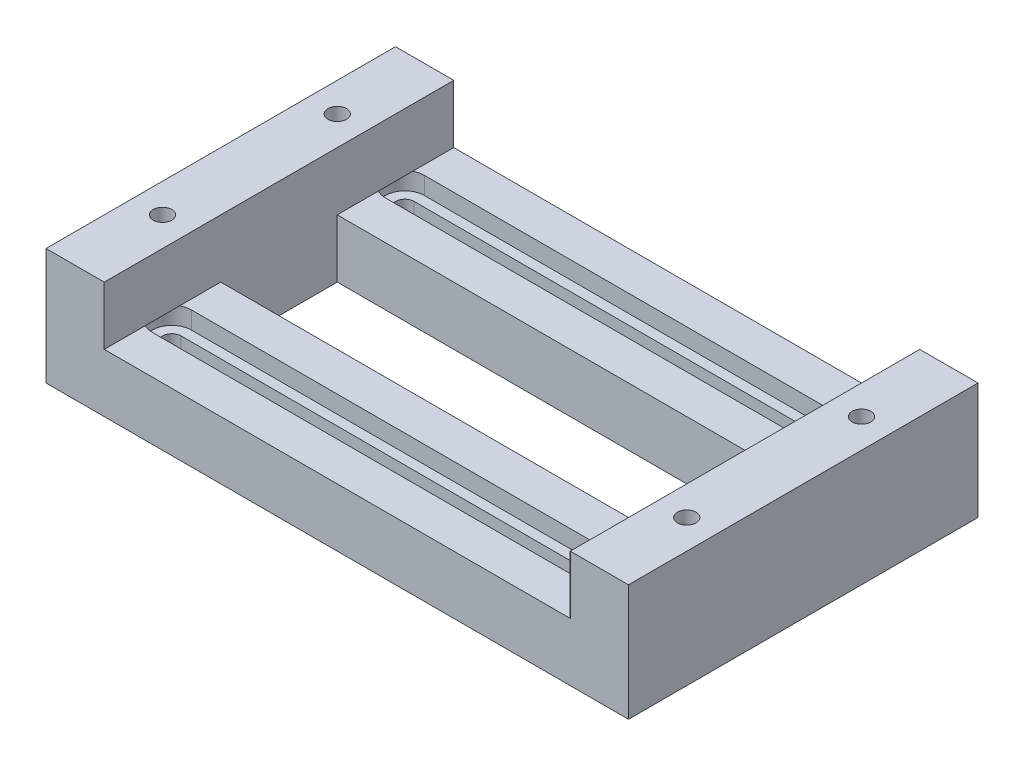
SolidWorks part; units mm, degrees
ref_plane "Front Plane" through (0, 0, 0) normal (0, 0, 1) x (1, 0, 0)
ref_plane "Top Plane" through (0, 0, 0) normal (0, 1, 0) x (1, 0, 0)
ref_plane "Right Plane" through (0, 0, 0) normal (1, 0, 0) x (0, 0, -1)
sketch "Sketch1" plane through (0, 0, 0) normal (0, 1, 0) x (1, 0, 0)
  line L0 (10, 40) -> (10, 20)
  line L1 (0, 0) -> (100, 0)
  line L2 (0, 0) -> (0, 60)
  line L3 (0, 60) -> (100, 60)
  line L4 (100, 0) -> (100, 60)
  line L5 (10, 20) -> (90, 20)
  line L6 (90, 20) -> (90, 40)
  line L7 (90, 40) -> (10, 40)
  line L8 (11.6, 10) -> (88.4, 10) construction
  line L9 (11.6, 11.6) -> (88.4, 11.6)
  line L10 (11.6, 8.4) -> (88.4, 8.4)
  line L11 (88.4, 50) -> (11.6, 50) construction
  line L12 (88.4, 48.4) -> (11.6, 48.4)
  line L13 (50, 0) -> (50, 20) construction
  line L14 (50, 40) -> (50, 60)
  line L15 (88.4, 51.6) -> (11.6, 51.6)
  circle A7 centre (5, 45) radius 1.6
  arc A22 (11.6, 11.6) -> (11.6, 8.4) centre (11.6, 10) ccw
  arc A23 (88.4, 8.4) -> (88.4, 11.6) centre (88.4, 10) ccw
  arc A24 (88.4, 48.4) -> (88.4, 51.6) centre (88.4, 50) ccw
  arc A25 (11.6, 51.6) -> (11.6, 48.4) centre (11.6, 50) ccw
  circle A29 centre (5, 15) radius 1.6
  circle A46 centre (95, 45) radius 1.6
  circle A47 centre (95, 15) radius 1.6
  point P14 (50, 50)
  point P17 (50, 10)
  point P22 (50, 50)
  point P33 (50, 10)
  point P34 (90, 10)
  point P35 (10, 10)
  point P36 (90, 50)
  point P37 (10, 50)
  dimension "D25" = 3.2
  dimension "D4" = 3.2
  dimension "D18" = 3.2
  dimension "D19" = 3.2
  dimension "D1" = 60
  dimension "D2" = 100
  dimension "D3" = 10
  dimension "D22" = 20
  dimension "D23" = 20
  dimension "D24" = 10
  dimension "D28" = 15
  dimension "D5" = 15
  dimension "D6" = 5
  dimension "D8" = 5
  dimension "D9" = 15
  dimension "D13" = 5
  dimension "D16" = 5
  dimension "D17" = 15
  dimension "D7" = 3.2
  dimension "D10" = 3.2
  dimension "D11" = 80
  dimension "D12" = 80
extrude "Boss-Extrude1" add sketch "Sketch1" along normal blind 10 contours L1 L4 L3 L2 A47 A46 A29 A7 L7 L6 L5 L0 region at (75, 0, -58.8338)
sketch "Sketch3" plane through (0, 10, 0) normal (0, 1, 0) x (1, 0, 0)
  line L4 (88.4, 53.35) -> (11.6, 53.35)
  line L5 (11.6, 46.65) -> (88.4, 46.65)
  line L6 (88.4, 13.35) -> (11.6, 13.35)
  line L7 (11.6, 6.65) -> (88.4, 6.65)
  line L8 (88.4, 13.35) -> (11.6, 13.35)
  line L9 (11.6, 6.65) -> (88.4, 6.65)
  line L10 (88.4, 53.35) -> (11.6, 53.35)
  line L11 (11.6, 46.65) -> (88.4, 46.65)
  arc A4 (88.4, 46.65) -> (88.4, 53.35) centre (88.4, 50) ccw
  arc A5 (11.6, 53.35) -> (11.6, 46.65) centre (11.6, 50) ccw
  arc A6 (11.6, 13.35) -> (11.6, 6.65) centre (11.6, 10) ccw
  arc A7 (88.4, 6.65) -> (88.4, 13.35) centre (88.4, 10) ccw
  arc A8 (11.6, 13.35) -> (11.6, 6.65) centre (11.6, 10) ccw
  arc A9 (88.4, 6.65) -> (88.4, 13.35) centre (88.4, 10) ccw
  arc A10 (88.4, 46.65) -> (88.4, 53.35) centre (88.4, 50) ccw
  arc A11 (11.6, 53.35) -> (11.6, 46.65) centre (11.6, 50) ccw
  dimension "D1" = 1.75
  dimension "D2" = 1.75
extrude "Cut-Slot insets" cut sketch "Sketch3" against normal blind 3
sketch "Sketch5" plane through (0, 10, 0) normal (0, 1, 0) x (1, 0, 0)
  line L2 (0, 60) -> (100, 60) construction
  line L3 (10, 60) -> (0, 60)
  line L4 (0, 60) -> (0, 0)
  line L5 (0, 0) -> (10, 0)
  line L6 (0, 0) -> (100, 0) construction
  line L9 (90, 0) -> (100, 0)
  line L10 (100, 0) -> (100, 60)
  line L11 (100, 60) -> (90, 60)
  line L20 (90, 60) -> (90, 0)
  line L21 (90, 20) -> (90, 40) construction
  line L22 (10, 0) -> (10, 60)
  line L23 (10, 40) -> (10, 20) construction
  circle A0 centre (95, 45) radius 1.6
  circle A3 centre (95, 15) radius 1.6
  circle A5 centre (5, 15) radius 1.6
  circle A8 centre (5, 45) radius 1.6
  circle A9 centre (5, 15) radius 1.6 construction
  circle A10 centre (5, 45) radius 1.6 construction
  circle A11 centre (95, 45) radius 1.6 construction
  circle A12 centre (95, 15) radius 1.6 construction
extrude "Boss-Extrude3" add sketch "Sketch5" along normal blind 10
sketch "Sketch6" plane through (0, 0, 0) normal (0, -1, 0) x (1, 0, 0)
  circle A0 centre (5, -45) radius 3.75
  circle A2 centre (5, -15) radius 3.75
  circle A3 centre (95, -15) radius 3.75
  circle A5 centre (95, -45) radius 3.75
  dimension "D1" = 7.5
  dimension "D3" = 7.5
  dimension "D4" = 7.5
  dimension "D6" = 7.5
extrude "Cut-Extrude1" cut sketch "Sketch6" against normal blind 2.5
equation "\"boltdiameter\"=3.2"
equation "\"D25@Sketch1\"=\"boltdiameter\""
equation "\"D4@Sketch1\"=\"boltdiameter\""
equation "\"D18@Sketch1\"=\"boltdiameter\""
equation "\"D19@Sketch1\"=\"boltdiameter\""
equation "\"boltfacediameter\"=7"
equation "\"boltFaceOffset\"= 1.75"
equation "\"D1@Sketch3\" = \"boltFaceOffset\""
equation "\"D2@Sketch3\" = \"boltFaceOffset\""
equation "\"screwInset\"=7.5"
equation "\"D1@Sketch6\"=\"screwInset\""
equation "\"D3@Sketch6\"=\"screwInset\""
equation "\"D4@Sketch6\"=\"screwInset\""
equation "\"D6@Sketch6\"=\"screwInset\""
equation "\"D7@Sketch1\"=\"boltdiameter\""
equation "\"D10@Sketch1\"=\"boltdiameter\""
equation "\"slotLength\"=80"
equation "\"D11@Sketch1\"=\"slotLength\""
equation "\"D12@Sketch1\"=\"slotLength\""
